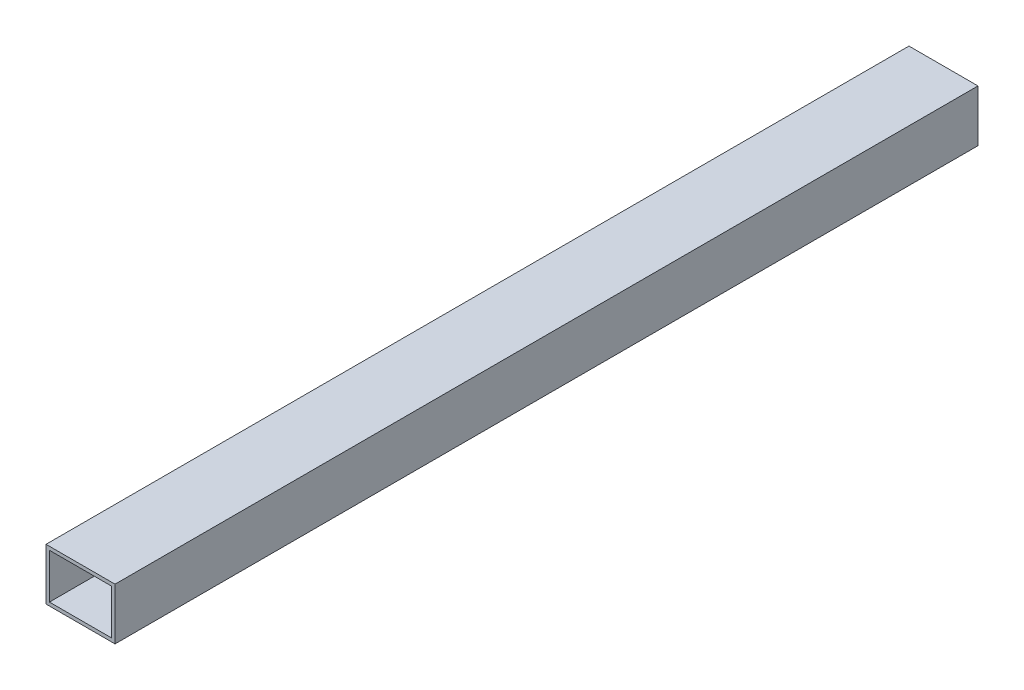
SolidWorks part; units mm, degrees
material "1060 合金"
ref_plane "前视基准面" through (0, 0, 0) normal (0, 0, 1) x (1, 0, 0)
ref_plane "上视基准面" through (0, 0, 0) normal (0, 1, 0) x (1, 0, 0)
ref_plane "右视基准面" through (0, 0, 0) normal (1, 0, 0) x (0, 0, -1)
other "Configuration Table"
sketch "草图1" plane through (0, 0, 0) normal (0, 0, 1) x (1, 0, 0)
  line L1 (0, 0) -> (20, 0)
  line L2 (0, 0) -> (0, -15)
  line L3 (0, -15) -> (20, -15)
  line L4 (20, 0) -> (20, -15)
  dimension "D1" = 15
  dimension "D2" = 20
extrude "拉伸-薄壁1" add sketch "草图1" along normal blind 250 thin thin type one direction reverse wall 1
